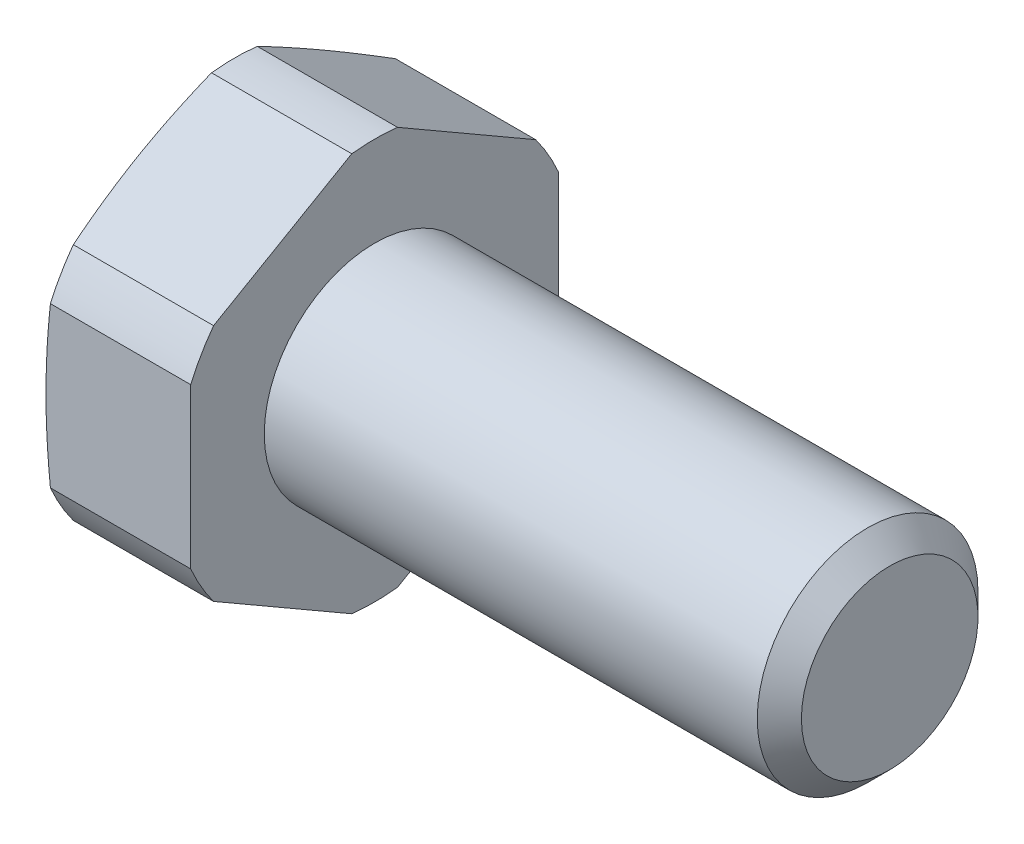
SolidWorks part; units mm, degrees
material "AISI 1020"
ref_plane "Спереди" through (0, 0, 0) normal (0, 0, 1) x (1, 0, 0)
ref_plane "Сверху" through (0, 0, 0) normal (0, 1, 0) x (1, 0, 0)
ref_plane "Справа" through (0, 0, 0) normal (1, 0, 0) x (0, 0, -1)
sketch "Эскиз1" plane through (0, 0, 0) normal (0, 0, 1) x (1, 0, 0)
  line L0 (-1000, 0) -> (49000, 0) construction
  line L1 (-4, 0) -> (-4, 4.75)
  line L2 (-4, 4.75) -> (-3.8124, 5.45)
  line L3 (-3.8124, 5.45) -> (0, 5.45)
  line L4 (0, 5.45) -> (0, 3)
  line L5 (0, 3) -> (13.4, 3)
  line L6 (14, 2.4) -> (14, 0)
  line L7 (14, 3) -> (14.5, 3.866) construction
  line L8 (14.5, 3.866) -> (15, 3) construction
  line L9 (15, 3) -> (14, 3) construction
  line L10 (14.5, 3.866) -> (14.5, 3) construction
  line L11 (14.5, 3.866) -> (0.5, 3.866) construction
  line L12 (13.4, 3) -> (14, 2.4)
  line L13 (14, 3) -> (13.7, 2.7) construction
  line L14 (-4, 4.75) -> (-14, 4.75) construction
  line L15 (-4, 0) -> (14, 0)
  dimension "D1" = 0.6
  dimension "D2" = 15
revolve "Повернуть1" add sketch "Эскиз1" angle 360 about L0
cosmetic thread "Условное изображение резьбы1" parameters "D1"=14, "D2"=4.2679
sketch "Эскиз2" plane through (-4, 0, 0) normal (-1, 0, 0) x (0, 0, 1)
  line L1 (0, 5.7735) -> (-5, 2.8868)
  line L2 (-5, 2.8868) -> (-5, -2.8868)
  line L3 (-5, -2.8868) -> (0, -5.7735)
  line L4 (0, -5.7735) -> (5, -2.8868)
  line L5 (5, -2.8868) -> (5, 2.8868)
  line L6 (5, 2.8868) -> (0, 5.7735)
  circle A0 centre (0, 0) radius 5 construction
  dimension "D1" = 10
extrude "Вырез-Вытянуть1" cut sketch "Эскиз2" against normal up to surface (18 mm away) flip side to cut up to face at (14, 0, 2.4)
equation "\"D1@Эскиз1\"=\"_d_@Эскиз1\"/10"
equation "\"D@Эскиз1\"=\"S_@Эскиз1\"*0.95"
equation "\"D1@Эскиз2\"=\"S_@Эскиз1\""
equation "\"D1@Условное изображение резьбы1\"=\"b_@Эскиз1\""
equation "\"D2@Условное изображение резьбы1\"=\"_d_@Эскиз1\"-\"dr@Эскиз1\"*2"
